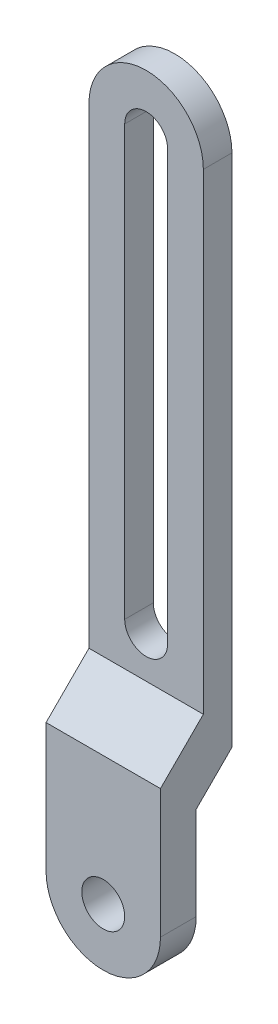
SolidWorks part; units mm, degrees
ref_plane "Płaszczyzna przednia" through (0, 0, 0) normal (0, 0, 1) x (1, 0, 0)
ref_plane "Płaszczyzna górna" through (0, 0, 0) normal (0, 1, 0) x (1, 0, 0)
ref_plane "Płaszczyzna prawa" through (0, 0, 0) normal (1, 0, 0) x (0, 0, -1)
sketch "Szkic1" plane through (0, 0, 0) normal (0, 0, 1) x (1, 0, 0)
  line L0 (0, 0) -> (0, 45) construction
  line L1 (-4, 0) -> (-4, 45)
  line L2 (4, 0) -> (4, 45)
  line L3 (0, 45) -> (0, 15) construction
  line L4 (1.5, 45) -> (1.5, 15)
  line L5 (-1.5, 45) -> (-1.5, 15)
  circle A0 centre (0, 0) radius 1.5
  arc A1 (-4, 0) -> (4, 0) centre (0, 0) ccw
  arc A2 (4, 45) -> (-4, 45) centre (0, 45) ccw
  arc A3 (1.5, 45) -> (-1.5, 45) centre (0, 45) ccw
  arc A4 (-1.5, 15) -> (1.5, 15) centre (0, 15) ccw
  point P3 (0, 22.5)
  point P9 (0, 30)
  dimension "D1" = 3
  dimension "D2" = 4
  dimension "D5" = 1.5
  dimension "D3" = 45
  dimension "D4" = 30
extrude "Dodanie-wyciągnięcie1" add sketch "Szkic1" along normal blind 2
sketch "Szkic2" plane through (0, 0, 2) normal (0, 0, 1) x (1, 0, 0)
  line L0 (-4, 45) -> (-4, 0) construction
  line L1 (-4, 9) -> (4, 9)
  line L2 (-4, 9) -> (-4, 0)
  line L4 (4, 9) -> (4, 0)
  arc A0 (-4, 0) -> (4, 0) centre (0, 0) ccw
  circle A1 centre (0, 0) radius 1.5
  dimension "D1" = 9
extrude "Dodanie-wyciągnięcie2" add sketch "Szkic2" along normal blind 3
sketch "Szkic3" plane through (0, 0, 0) normal (0, 0, -1) x (-1, 0, 0)
  line L0 (-4, 0) -> (-4, 45) construction
  line L1 (-4, 7) -> (4, 7)
  line L2 (-4, 7) -> (-4, 0)
  line L4 (4, 7) -> (4, 0)
  arc A0 (-4, 0) -> (4, 0) centre (0, 0) ccw
  dimension "D1" = 7
extrude "Wytnij-wyciągnięcie1" cut sketch "Szkic3" against normal blind 2.5
chamfer "Sfazowanie1" distance 3 angle 45 1 edges at (0, 9, 2)
chamfer "Sfazowanie2" distance 2 angle 45 1 edges at (0, 7, 0)
chamfer "Sfazowanie3" distance 0.5 angle 45 1 edges at (0, 7, 2.5)
